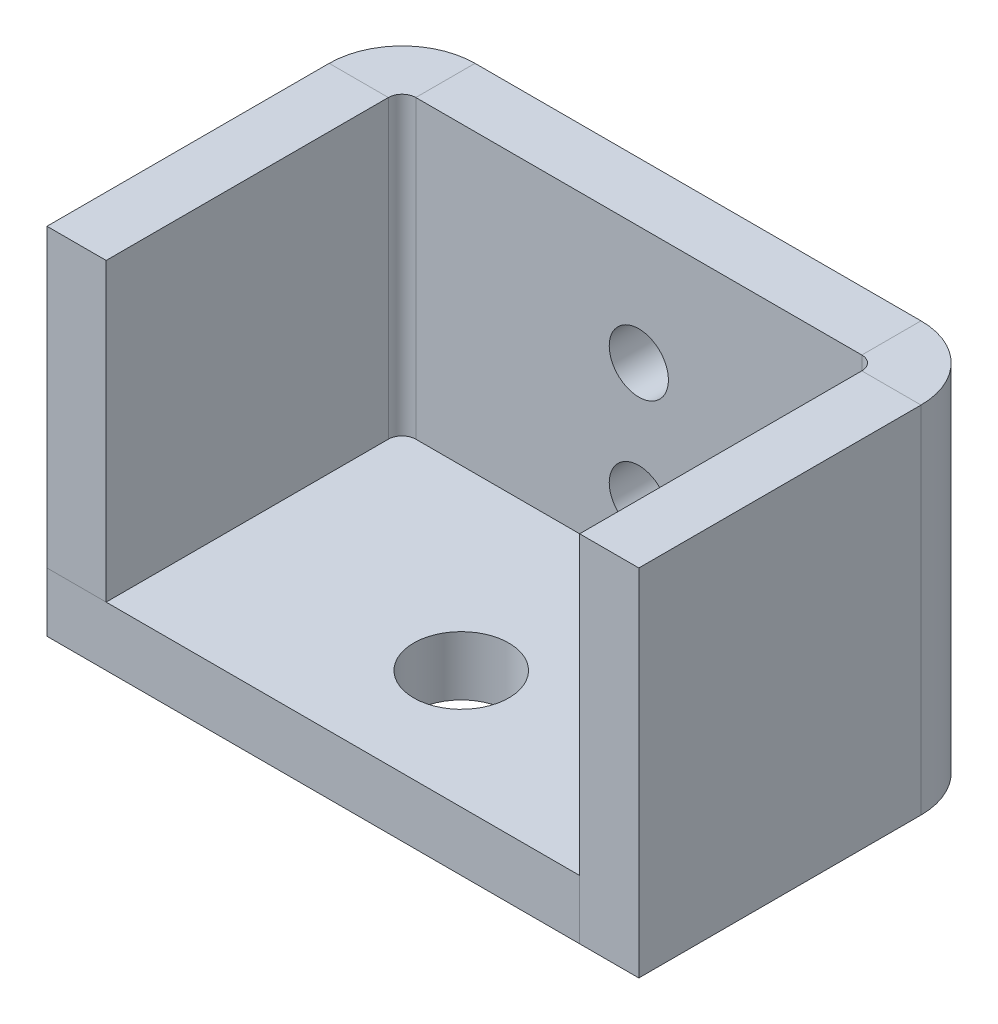
SolidWorks part; units mm, degrees
note: The reader was unsure of these and kept them because the rebuilt part matched: flange length of "Edge-Flange1", "Edge-Flange2".
material "AISI 316 Stainless Steel Sheet (SS)"
ref_plane "Front Plane" through (0, 0, 0) normal (0, 0, 1) x (1, 0, 0)
ref_plane "Top Plane" through (0, 0, 0) normal (0, 1, 0) x (1, 0, 0)
ref_plane "Right Plane" through (0, 0, 0) normal (1, 0, 0) x (0, 0, -1)
sketch "Sketch1" plane through (0, 0, 0) normal (0, 0, 1) x (1, 0, 0)
  line L0 (-12.7, 9.525) -> (-12.7, -9.525)
  line L1 (-12.7, -9.525) -> (12.7, -9.525)
  line L2 (12.7, -9.525) -> (12.7, 9.525)
  line L3 (12.7, 9.525) -> (-12.7, 9.525)
  line L4 (-12.7, 9.525) -> (12.7, -9.525) construction
  line L5 (12.7, 9.525) -> (-12.7, -9.525) construction
  point P2 (0, 0)
  dimension "D1" = 25.4
  dimension "D2" = 19.05
base flange "Base-Flange1" sketch "Sketch1" thickness 3.175 reverse thickness direction no parameters "D1"=0.7366
edge flange "Edge-Flange1" sketch "Sketch8" flange angle 90 flange length 19.05 flange position material outside bend radius 0.7366 thickness 3.175 relief rectangular parameters "D6"=10
sketch "Sketch8" plane through (12.7, 0, 0) normal (1, 0, 0) x (0, 1, 0)
  line L2 (-9.525, 0) -> (-9.525, 15.875)
  line L3 (-9.525, 15.875) -> (9.525, 15.875)
  line L4 (9.525, 15.875) -> (9.525, 0)
  line L7 (-9.525, 0) -> (9.525, 0) construction
  line L8 (-9.525, 0) -> (9.525, 0)
bend "EdgeBend1" bend radius 0.7366 bend angle 90 parameters "D5"=1
edge flange "Edge-Flange2" sketch "Sketch11" flange angle 90 flange length 19.05 flange position material outside bend radius 0.7366 thickness 3.175 relief rectangular parameters "D6"=10
sketch "Sketch11" plane through (-12.7, 0, 0) normal (-1, 0, 0) x (0, -1, 0)
  line L2 (-9.525, 0) -> (-9.525, 15.875)
  line L3 (-9.525, 15.875) -> (9.525, 15.875)
  line L4 (9.525, 15.875) -> (9.525, 0)
  line L7 (-9.525, 0) -> (9.525, 0) construction
  line L8 (-9.525, 0) -> (9.525, 0)
bend "EdgeBend2" bend radius 0.7366 bend angle 90 parameters "D5"=2
ref_plane "Plane1" through (-11.9634, -9.525, 0) normal (1, 0, 0) x (0, 0, -1)
ref_plane "Plane2" through (-11.9634, -9.525, -3.175) normal (1, 0, 0) x (0, 0, -1)
sketch "Sketch32" plane through (0, -9.525, 0) normal (0, -1, 0) x (1, 0, 0)
  line L0 (-15.875, 15.875) -> (-15.875, 0.7366)
  line L1 (-15.875, 15.875) -> (15.875, 15.875)
  line L2 (15.875, 15.875) -> (15.875, 0.7366)
  line L3 (-11.9634, -9.7549) -> (-11.9634, 3.4049) construction
  line L4 (-11.9634, -3.175) -> (11.9634, -3.175)
  arc A0 (15.875, 0.7366) -> (11.9634, -3.175) centre (11.9634, 0.7366) cw
  arc A1 (-15.875, 0.7366) -> (-11.9634, -3.175) centre (-11.9634, 0.7366) ccw
  arc A2 (-15.875, 0.7366) -> (-11.9634, -3.175) centre (-11.9634, 0.7366) ccw construction
base flange "Base-Flange2" sketch "Sketch32" thickness 3.175 reverse thickness direction no parameters "D1"=0.7366
sketch "Sketch35" plane through (0, 0, -3.175) normal (0, 0, -1) x (-1, 0, 0)
  line L0 (0, 9.525) -> (0, -6.35) construction
  line L1 (-11.9634, 9.525) -> (11.9634, 9.525) construction
  line L2 (11.9634, -6.35) -> (-11.9634, -6.35) construction
  line L3 (-11.9634, 3.175) -> (11.9634, 3.175) construction
  line L4 (-11.9634, 9.525) -> (-11.9634, -9.525) construction
  line L5 (11.9634, -9.525) -> (11.9634, 9.525) construction
  circle A0 centre (0, 3.175) radius 1.5875
  circle A1 centre (0, -4.7625) radius 1.5875 [skipped]
  circle A2 centre (0, -3.175) radius 1.5875
  circle A3 centre (0, -9.525) radius 1.5875
  circle A4 centre (0, -15.875) radius 1.5875
  circle A5 centre (0, -22.225) radius 1.5875
  dimension "D2" = 3.175
  dimension "D3" = 2
  dimension "D1" = 6.35
  dimension "D4" = 14.2875
  dimension "D5" = 5
extrude "Cut-Extrude2" cut sketch "Sketch35" against normal through all
sketch "Sketch36" plane through (0, -6.35, 0) normal (0, 1, 0) x (1, 0, 0)
  line L0 (0, -15.875) -> (0, 3.175) construction
  line L1 (-15.875, -15.875) -> (15.875, -15.875) construction
  line L2 (11.9634, 3.175) -> (-11.9634, 3.175) construction
  line L3 (-15.875, -9.525) -> (15.875, -9.525) construction
  line L4 (-15.875, -15.875) -> (-15.875, -0.7366) construction
  line L5 (15.875, -0.7366) -> (15.875, -15.875) construction
  line L6 (15.875, -15.875) -> (-15.875, -15.875) construction
  circle A0 centre (0, -9.525) radius 3.048
  dimension "D2" = 6.096
  dimension "D1" = 6.35
hole_wizard "Tap Drill for 1/4-20 Tap1" positions "Sketch44" profile "Sketch45" hole size "1/4-20" standard "ANSI Inch" end condition through all
sketch "Sketch44" plane through (0, -6.35, 0) normal (0, 1, 0) x (1, 0, 0)
  point P0 (0, -9.525)
sketch "Sketch45" plane through (0, -6.35, 9.525) normal (1, 0, 0) x (0, 0, 1)
  line L0 (0, 0) -> (0, 3.175)
  line L1 (0, 3.175) -> (2.5527, 3.175)
  line L2 (2.5527, 3.175) -> (2.5527, 0)
  line L5 (2.5527, 0) -> (0, 0)
  line L11 (0, -6.35) -> (0, 107.95) construction
  dimension "Thru Hole Dia." = 5.1054
  dimension "Thru Hole Depth" = 3.175
sketch "Bend-Lines1" [suppressed] plane through (0, 0, 0) normal (0, 1, 0) x (1, 0, 0)
sketch "Bounding-Box1" [suppressed] plane through (0, 0, 0) normal (0, 1, 0) x (1, 0, 0)
sheet metal parameters "Sheet-Metal1" thickness 3.175 parameters "D1"=0.7366
flat pattern "Flat-Pattern1" [suppressed]
sketch "Bend-Lines2" plane through (0, 0, 0) normal (0, 1, 0) x (1, 0, 0)
sketch3d "Bounding-Box2" [suppressed]
  line L0 (-12.7, 38.1, 0) -> (-12.7, -38.1, 0) construction
  line L1 (12.7, 38.1, 0) -> (12.7, -38.1, 0) construction
  line L2 (-12.7, 38.1, 0) -> (12.7, 38.1, 0) construction
  line L3 (-12.7, -38.1, 0) -> (12.7, -38.1, 0) construction
sheet metal parameters "Sheet-Metal2" thickness 3.175 parameters "D1"=0.7366
flat pattern "Flat-Pattern1"
sketch "Bend-Lines2" plane through (0, 0, 0) normal (0, 0, 1) x (1, 0, 0)
  line L0 (13.7887, -38.1) -> (13.7887, 38.1) construction
  line L1 (13.7887, -38.1) -> (13.7887, 38.1) construction
sketch3d "Bounding-Box2" [suppressed]
  line L0 (30.7525, 38.1, 0) -> (30.7525, -38.1, 0) construction
  line L1 (-12.7, 38.1, 0) -> (-12.7, -38.1, 0) construction
  line L2 (30.7525, 38.1, 0) -> (-12.7, 38.1, 0) construction
  line L3 (30.7525, -38.1, 0) -> (-12.7, -38.1, 0) construction
bend of the flat pattern "Flatten-<EdgeBend1>1"
sheet metal parameters "Sheet-Metal3" thickness 3.175 parameters "D1"=0.7366
flat pattern "Flat-Pattern1"
sketch "Bend-Lines2" plane through (0, 0, 0) normal (0, 0, 1) x (1, 0, 0)
  line L0 (13.7887, -38.1) -> (13.7887, 38.1) construction
  line L1 (13.7887, -38.1) -> (13.7887, 38.1) construction
  line L2 (-13.7887, 38.1) -> (-13.7887, -38.1) construction
  line L3 (-13.7887, 38.1) -> (-13.7887, -38.1) construction
sketch3d "Bounding-Box2" [suppressed]
  line L0 (30.7525, 38.1, 0) -> (30.7525, -38.1, 0) construction
  line L1 (-30.7525, 38.1, 0) -> (-30.7525, -38.1, 0) construction
  line L2 (30.7525, 38.1, 0) -> (-30.7525, 38.1, 0) construction
  line L3 (30.7525, -38.1, 0) -> (-30.7525, -38.1, 0) construction
bend of the flat pattern "Flatten-<EdgeBend1>1"
bend of the flat pattern "Flatten-<EdgeBend2>1"
sheet metal parameters "Sheet-Metal6" thickness 3.175 parameters "D1"=0.7366
flat pattern "Flat-Pattern6" [suppressed]
sketch "Bend-Lines3" plane through (0, 0, 0) normal (0, 1, 0) x (1, 0, 0)
sketch3d "Bounding-Box3" [suppressed]
  line L0 (27.8384, -15.1384, 0) -> (-3.9116, -15.1384, 0) construction
  line L1 (27.8384, 3.9116, 0) -> (-3.9116, 3.9116, 0) construction
  line L2 (27.8384, -15.1384, 0) -> (27.8384, 3.9116, 0) construction
  line L3 (-3.9116, -15.1384, 0) -> (-3.9116, 3.9116, 0) construction
sketch "Sketch36-1" [suppressed] plane through (0, -34.925, 0) normal (0, 1, 0) x (1, 0, 0)
  line L0 (0, -15.875) -> (0, 3.175) construction
  line L3 (-15.875, -9.525) -> (15.875, -9.525) construction
  line L6 (15.875, -15.875) -> (-15.875, -15.875) construction
  circle A0 centre (0, -9.525) radius 3.048
  dimension "D2" = 6.096
  dimension "D1" = 6.35
sheet metal parameters "Sheet-Metal8" thickness 3.175 parameters "D1"=0.7366
flat pattern "Flat-Pattern1"
sketch "Bend-Lines2" plane through (0, 0, 0) normal (0, 0, 1) x (1, 0, 0)
  line L0 (13.7887, -9.525) -> (13.7887, 9.525) construction
  line L1 (13.7887, -9.525) -> (13.7887, 9.525) construction
  line L2 (-13.7887, 9.525) -> (-13.7887, -9.525) construction
  line L3 (-13.7887, 9.525) -> (-13.7887, -9.525) construction
sketch3d "Bounding-Box2" [suppressed]
  line L0 (-30.7525, -9.525, 0) -> (30.7525, -9.525, 0) construction
  line L1 (-30.7525, 9.525, 0) -> (30.7525, 9.525, 0) construction
  line L2 (-30.7525, -9.525, 0) -> (-30.7525, 9.525, 0) construction
  line L3 (30.7525, -9.525, 0) -> (30.7525, 9.525, 0) construction
bend of the flat pattern "Flatten-<EdgeBend1>1"
bend of the flat pattern "Flatten-<EdgeBend2>1"
sheet metal parameters "Sheet-Metal10" thickness 3.175 parameters "D1"=0.7366
flat pattern "Flat-Pattern6" [suppressed]
sketch "Bend-Lines3" plane through (0, 0, 0) normal (0, 1, 0) x (1, 0, 0)
sketch3d "Bounding-Box3" [suppressed]
  line L0 (27.8384, -15.1384, 0) -> (-3.9116, -15.1384, 0) construction
  line L1 (27.8384, 3.9116, 0) -> (-3.9116, 3.9116, 0) construction
  line L2 (27.8384, -15.1384, 0) -> (27.8384, 3.9116, 0) construction
  line L3 (-3.9116, -15.1384, 0) -> (-3.9116, 3.9116, 0) construction
sketch "Sketch36-1" [suppressed] plane through (0, -6.35, 0) normal (0, 1, 0) x (1, 0, 0)
  line L0 (0, -15.875) -> (0, 3.175) construction
  line L3 (-15.875, -9.525) -> (15.875, -9.525) construction
  line L6 (15.875, -15.875) -> (-15.875, -15.875) construction
  circle A0 centre (0, -9.525) radius 3.048
  dimension "D2" = 6.096
  dimension "D1" = 6.35
